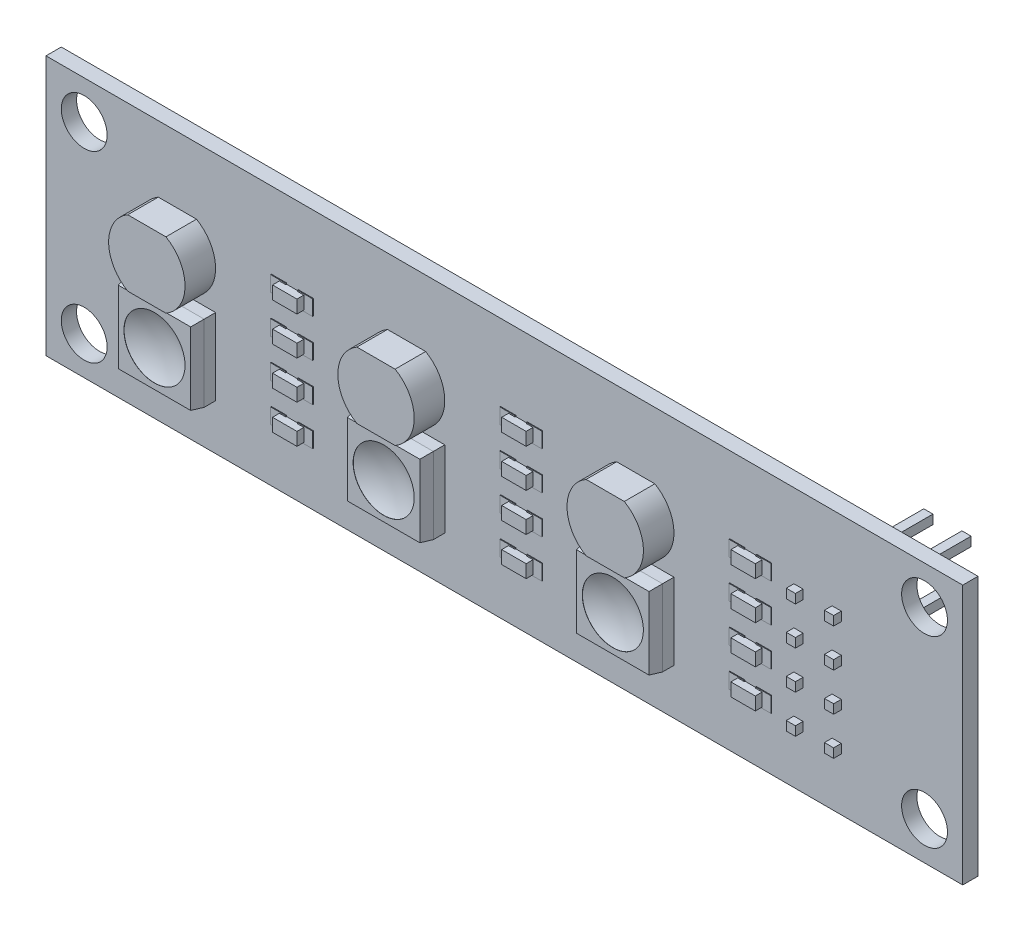
SolidWorks part; units mm, degrees
ref_plane "Alzado" through (0, 0, 0) normal (0, 0, 1) x (1, 0, 0)
ref_plane "Planta" through (0, 0, 0) normal (0, 1, 0) x (1, 0, 0)
ref_plane "Vista lateral" through (0, 0, 0) normal (1, 0, 0) x (0, 0, -1)
sketch "Croquis1" plane through (0, 0, 0) normal (0, 0, 1) x (1, 0, 0)
  line L0 (0, 8.5) -> (0, -8.5) construction
  line L1 (30, -8.5) -> (-30, -8.5)
  line L2 (30, -8.5) -> (30, 8.5)
  line L3 (30, 8.5) -> (-30, 8.5)
  line L4 (-30, -8.5) -> (-30, 8.5)
  line L5 (30, -8.5) -> (-30, 8.5) construction
  line L6 (30, 8.5) -> (-30, -8.5) construction
  line L7 (-30, 0) -> (30, 0) construction
  circle A0 centre (-27.5, 6) radius 1.5
  circle A1 centre (-27.5, -6) radius 1.5
  circle A2 centre (27.5, -6) radius 1.5
  circle A3 centre (27.5, 6) radius 1.5
  point P0 (0, 0)
  dimension "D5" = 3
  dimension "D1" = 60
  dimension "D2" = 17
  dimension "D3" = 2.5
  dimension "D4" = 2.5
extrude "Saliente-Extruir1" add sketch "Croquis1" along normal blind 1
sketch "Croquis2" plane through (0, 0, 1) normal (0, 0, 1) x (1, 0, 0)
  line L0 (-30, 8.5) -> (-30, -8.5) construction
  line L1 (-23.9, -5.5) -> (-18.9, -5.5)
  line L2 (-23.9, -5.5) -> (-23.9, -0.5)
  line L3 (-23.9, -0.5) -> (-18.9, -0.5)
  line L4 (-18.9, -5.5) -> (-18.9, -0.5)
  line L5 (-23.9, -5.5) -> (-18.9, -0.5) construction
  line L6 (-23.9, -0.5) -> (-18.9, -5.5) construction
  line L7 (-30, -8.5) -> (30, -8.5) construction
  point P0 (-21.4, -3)
  dimension "D1" = 8.6
  dimension "D2" = 5.5
  dimension "D3" = 5
  dimension "D4" = 5
extrude "Saliente-Extruir2" add sketch "Croquis2" along normal blind 0.75
sketch "Croquis3" plane through (0, 0, 1.75) normal (0, 0, 1) x (1, 0, 0)
  line L4 (-18.9, -5.5) -> (-18.9, -0.5)
  line L5 (-18.9, -0.5) -> (-23.9, -0.5)
  line L6 (-23.9, -0.5) -> (-23.9, -5.5)
  line L7 (-23.9, -5.5) -> (-18.9, -5.5)
  line L8 (-18.9, -5.5) -> (-18.9, -0.5)
  line L9 (-18.9, -0.5) -> (-23.9, -0.5)
  line L10 (-23.9, -0.5) -> (-23.9, -5.5)
  line L11 (-23.9, -5.5) -> (-18.9, -5.5)
  dimension "D1" = 0
extrude "Saliente-Extruir3" add sketch "Croquis3" along normal blind 0.75 draft 10
sketch "Croquis4" plane through (0, 0, 2.5) normal (0, 0, 1) x (1, 0, 0)
  line L0 (-23.7678, -0.6322) -> (-19.0322, -5.3678) construction
  circle A0 centre (-21.4, -3) radius 2
  dimension "D1" = 4
extrude "Cortar-Extruir1" cut sketch "Croquis4" against normal blind 0.01
dome "Cúpula1" faces to dome 1 distance 0.5 reverse direction yes elliptical dome no face at (-19.4, -3, 2.49) parameters "D1"=0.5
pattern_linear "MatrizL6" count 3 spacing 15 along (1, 0, 0) of "Saliente-Extruir2", "Saliente-Extruir3", "Cúpula1", "Cortar-Extruir1"
sketch "Croquis5" plane through (0, 0, 1) normal (0, 0, 1) x (1, 0, 0)
  line L0 (-21.4, -8.5) -> (-21.4, 8.5) construction
  line L1 (-30, -8.5) -> (30, -8.5) construction
  line L2 (30, 8.5) -> (-30, 8.5) construction
  line L3 (-22.65, 4.1651) -> (-20.15, 4.1651)
  line L4 (-23.9, 2) -> (-18.9, 2) construction
  line L5 (-19.0322, -0.6322) -> (-23.7678, -0.6322) construction
  line L6 (-22.65, -0.1651) -> (-20.15, -0.1651)
  arc A0 (-22.65, 4.1651) -> (-22.65, -0.1651) centre (-21.4, 2) ccw
  arc A1 (-20.15, -0.1651) -> (-20.15, 4.1651) centre (-21.4, 2) ccw
  point P13 (-21.4, -0.6322)
  dimension "D1" = 6.5
  dimension "D2" = 5
  dimension "D3" = 2.5
extrude "Saliente-Extruir4" add sketch "Croquis5" along normal blind 2
pattern_linear "MatrizL7" count 3 spacing 15 along (1, 0, 0) of "Saliente-Extruir4"
sketch "Croquis6" plane through (0, 0, 1) normal (0, 0, 1) x (1, 0, 0)
  line L0 (-30, -8.5) -> (30, -8.5) construction
  line L1 (-15.25, -4) -> (-14.25, -4)
  line L2 (-15.25, -4) -> (-15.25, -5)
  line L3 (-15.25, -5) -> (-14.25, -5)
  line L4 (-14.25, -4) -> (-14.25, -5)
  line L5 (-15.25, -4) -> (-14.25, -5) construction
  line L6 (-15.25, -5) -> (-14.25, -4) construction
  line L7 (-30, 8.5) -> (-30, -8.5) construction
  line L8 (-13.5, -5) -> (-12.5, -5)
  line L9 (-13.5, -5) -> (-13.5, -4)
  line L10 (-13.5, -4) -> (-12.5, -4)
  line L11 (-12.5, -5) -> (-12.5, -4)
  line L12 (-13.5, -5) -> (-12.5, -4) construction
  line L13 (-13.5, -4) -> (-12.5, -5) construction
  line L14 (-0.25, -4) -> (-0.25, -5)
  line L15 (-0.25, -4) -> (0.75, -4)
  line L16 (-0.25, -5) -> (0.75, -5)
  line L17 (0.75, -4) -> (0.75, -5)
  line L18 (1.5, -5) -> (1.5, -4)
  line L19 (1.5, -5) -> (2.5, -5)
  line L20 (2.5, -5) -> (2.5, -4)
  line L21 (1.5, -4) -> (2.5, -4)
  line L22 (14.75, -4) -> (14.75, -5)
  line L23 (14.75, -4) -> (15.75, -4)
  line L24 (14.75, -5) -> (15.75, -5)
  line L25 (15.75, -4) -> (15.75, -5)
  line L26 (16.5, -5) -> (16.5, -4)
  line L27 (16.5, -5) -> (17.5, -5)
  line L28 (17.5, -5) -> (17.5, -4)
  line L29 (16.5, -4) -> (17.5, -4)
  line L30 (-0.25, -1.5) -> (-0.25, -2.5)
  line L31 (-0.25, -1.5) -> (0.75, -1.5)
  line L32 (-0.25, -2.5) -> (0.75, -2.5)
  line L33 (0.75, -1.5) -> (0.75, -2.5)
  line L34 (1.5, -2.5) -> (1.5, -1.5)
  line L35 (1.5, -2.5) -> (2.5, -2.5)
  line L36 (2.5, -2.5) -> (2.5, -1.5)
  line L37 (1.5, -1.5) -> (2.5, -1.5)
  line L38 (14.75, -1.5) -> (14.75, -2.5)
  line L39 (14.75, -1.5) -> (15.75, -1.5)
  line L40 (14.75, -2.5) -> (15.75, -2.5)
  line L41 (15.75, -1.5) -> (15.75, -2.5)
  line L42 (16.5, -2.5) -> (16.5, -1.5)
  line L43 (16.5, -2.5) -> (17.5, -2.5)
  line L44 (17.5, -2.5) -> (17.5, -1.5)
  line L45 (16.5, -1.5) -> (17.5, -1.5)
  line L46 (-0.25, 1) -> (-0.25, 0)
  line L47 (-0.25, 1) -> (0.75, 1)
  line L48 (-0.25, 0) -> (0.75, 0)
  line L49 (0.75, 1) -> (0.75, 0)
  line L50 (1.5, 0) -> (1.5, 1)
  line L51 (1.5, 0) -> (2.5, 0)
  line L52 (2.5, 0) -> (2.5, 1)
  line L53 (1.5, 1) -> (2.5, 1)
  line L54 (14.75, 1) -> (14.75, 0)
  line L55 (14.75, 1) -> (15.75, 1)
  line L56 (14.75, 0) -> (15.75, 0)
  line L57 (15.75, 1) -> (15.75, 0)
  line L58 (16.5, 0) -> (16.5, 1)
  line L59 (16.5, 0) -> (17.5, 0)
  line L60 (17.5, 0) -> (17.5, 1)
  line L61 (16.5, 1) -> (17.5, 1)
  line L62 (-0.25, 3.5) -> (-0.25, 2.5)
  line L63 (-0.25, 3.5) -> (0.75, 3.5)
  line L64 (-0.25, 2.5) -> (0.75, 2.5)
  line L65 (0.75, 3.5) -> (0.75, 2.5)
  line L66 (1.5, 2.5) -> (1.5, 3.5)
  line L67 (1.5, 2.5) -> (2.5, 2.5)
  line L68 (2.5, 2.5) -> (2.5, 3.5)
  line L69 (1.5, 3.5) -> (2.5, 3.5)
  line L70 (14.75, 3.5) -> (14.75, 2.5)
  line L71 (14.75, 3.5) -> (15.75, 3.5)
  line L72 (14.75, 2.5) -> (15.75, 2.5)
  line L73 (15.75, 3.5) -> (15.75, 2.5)
  line L74 (16.5, 2.5) -> (16.5, 3.5)
  line L75 (16.5, 2.5) -> (17.5, 2.5)
  line L76 (17.5, 2.5) -> (17.5, 3.5)
  line L77 (16.5, 3.5) -> (17.5, 3.5)
  line L78 (-15.25, -1.5) -> (-15.25, -2.5)
  line L79 (-15.25, -1.5) -> (-14.25, -1.5)
  line L80 (-15.25, -2.5) -> (-14.25, -2.5)
  line L81 (-14.25, -1.5) -> (-14.25, -2.5)
  line L82 (-13.5, -2.5) -> (-13.5, -1.5)
  line L83 (-13.5, -2.5) -> (-12.5, -2.5)
  line L84 (-12.5, -2.5) -> (-12.5, -1.5)
  line L85 (-13.5, -1.5) -> (-12.5, -1.5)
  line L86 (-15.25, 1) -> (-15.25, 0)
  line L87 (-15.25, 1) -> (-14.25, 1)
  line L88 (-15.25, 0) -> (-14.25, 0)
  line L89 (-14.25, 1) -> (-14.25, 0)
  line L90 (-13.5, 0) -> (-13.5, 1)
  line L91 (-13.5, 0) -> (-12.5, 0)
  line L92 (-12.5, 0) -> (-12.5, 1)
  line L93 (-13.5, 1) -> (-12.5, 1)
  line L94 (-15.25, 3.5) -> (-15.25, 2.5)
  line L95 (-15.25, 3.5) -> (-14.25, 3.5)
  line L96 (-15.25, 2.5) -> (-14.25, 2.5)
  line L97 (-14.25, 3.5) -> (-14.25, 2.5)
  line L98 (-13.5, 2.5) -> (-13.5, 3.5)
  line L99 (-13.5, 2.5) -> (-12.5, 2.5)
  line L100 (-12.5, 2.5) -> (-12.5, 3.5)
  line L101 (-13.5, 3.5) -> (-12.5, 3.5)
  point P0 (-14.75, -4.5)
  point P7 (-13, -4.5)
  dimension "D1" = 4
  dimension "D2" = 1.75
  dimension "D3" = 1
  dimension "D4" = 1
  dimension "D5" = 14.75
  dimension "D6" = 3
  dimension "D7" = 4
extrude "Saliente-Extruir5" add sketch "Croquis6" along normal blind 0.05
sketch "Croquis7" plane through (0, 0, 1) normal (0, 0, 1) x (1, 0, 0)
  line L0 (-15.25, -4) -> (-12.5, -5) construction
  line L1 (-15.25, -5) -> (-12.5, -4) construction
  line L2 (-14.25, -4) -> (-15.25, -4) construction
  line L3 (-14.675, -4.925) -> (-13.075, -4.925)
  line L4 (-14.675, -4.925) -> (-14.675, -4.075)
  line L5 (-14.675, -4.075) -> (-13.075, -4.075)
  line L6 (-13.075, -4.925) -> (-13.075, -4.075)
  line L7 (-14.675, -4.925) -> (-13.075, -4.075) construction
  line L8 (-14.675, -4.075) -> (-13.075, -4.925) construction
  line L9 (-15.25, -4) -> (-15.25, -5) construction
  point P8 (-13.875, -4.5)
  dimension "D1" = 1.6
  dimension "D2" = 0.85
extrude "Saliente-Extruir6" add sketch "Croquis7" along normal blind 0.5
pattern_linear "MatrizL8" count 3 spacing 15 along (1, 0, 0) count 4 spacing 2.5 along (0, 1, 0) of "Saliente-Extruir6"
sketch "Croquis8" plane through (0, 0, 1) normal (0, 0, 1) x (1, 0, 0)
  line L1 (18.5, -6) -> (22.5, -6)
  line L2 (18, -5.5) -> (18, -4)
  line L3 (18.5, -3.5) -> (22.5, -3.5)
  line L4 (23, -5.5) -> (23, -4)
  line L5 (18, -6) -> (23, -3.5) construction
  line L6 (18, -3.5) -> (23, -6) construction
  line L7 (-30, -8.5) -> (30, -8.5) construction
  line L8 (30, -8.5) -> (30, 8.5) construction
  line L9 (17.5, -2.5) -> (17.5, -1.5) construction
  arc A0 (22.5, -6) -> (23, -5.5) centre (22.5, -5.5) ccw
  arc A1 (22.5, -3.5) -> (23, -4) centre (22.5, -4) cw
  arc A2 (18.5, -6) -> (18, -5.5) centre (18.5, -5.5) cw
  arc A3 (18, -4) -> (18.5, -3.5) centre (18.5, -4) cw
  point P0 (20.5, -4.75)
  dimension "D5" = 0.5
  dimension "D1" = 0.5
  dimension "D2" = 2.5
  dimension "D3" = 5
  dimension "D4" = 2.5
extrude "Saliente-Extruir7" add sketch "Croquis8" against normal blind 2.5
sketch "Croquis9" plane through (0, 0, -1.5) normal (0, 0, -1) x (-1, 0, 0)
  line L0 (-20.5, -3.5) -> (-20.5, -6) construction
  line L1 (-18.5, -3.5) -> (-22.5, -3.5) construction
  line L2 (-18.5, -6) -> (-22.5, -6) construction
  line L3 (-20.5, -4.75) -> (-18, -4.75) construction
  line L4 (-18, -4) -> (-18, -5.5) construction
  line L5 (-21.45, -5.05) -> (-22.05, -5.05)
  line L6 (-19.55, -5.05) -> (-18.95, -5.05)
  line L7 (-19.55, -5.05) -> (-19.55, -4.45)
  line L8 (-19.55, -4.45) -> (-18.95, -4.45)
  line L9 (-18.95, -5.05) -> (-18.95, -4.45)
  line L10 (-19.55, -5.05) -> (-18.95, -4.45) construction
  line L11 (-19.55, -4.45) -> (-18.95, -5.05) construction
  line L12 (-21.45, -5.05) -> (-21.45, -4.45)
  line L13 (-21.45, -4.45) -> (-22.05, -4.45)
  line L14 (-22.05, -5.05) -> (-22.05, -4.45)
  point P11 (-19.25, -4.75)
  dimension "D1" = 0.6
extrude "Saliente-Extruir8" add sketch "Croquis9" along normal blind 6
pattern_linear "MatrizL9" count 4 spacing 2.5 along (0, 1, 0) of "Saliente-Extruir7", "Saliente-Extruir8"
sketch "Croquis10" plane through (0, 0, -7.5) normal (0, 0, -1) x (-1, 0, 0)
  line L4 (-21.45, -5.05) -> (-21.45, -4.45)
  line L5 (-21.45, -4.45) -> (-22.05, -4.45)
  line L6 (-22.05, -4.45) -> (-22.05, -5.05)
  line L7 (-22.05, -5.05) -> (-21.45, -5.05)
  line L8 (-21.45, -5.05) -> (-21.45, -4.45)
  line L9 (-21.45, -4.45) -> (-22.05, -4.45)
  line L10 (-22.05, -4.45) -> (-22.05, -5.05)
  line L11 (-22.05, -5.05) -> (-21.45, -5.05)
  dimension "D1" = 0
extrude "Saliente-Extruir9" add sketch "Croquis10" against normal blind 9
pattern_linear "MatrizL10" count 4 spacing 2.5 along (0, 1, 0) count 2 spacing 2.5 along (-1, 0, 0) of "Saliente-Extruir9"
